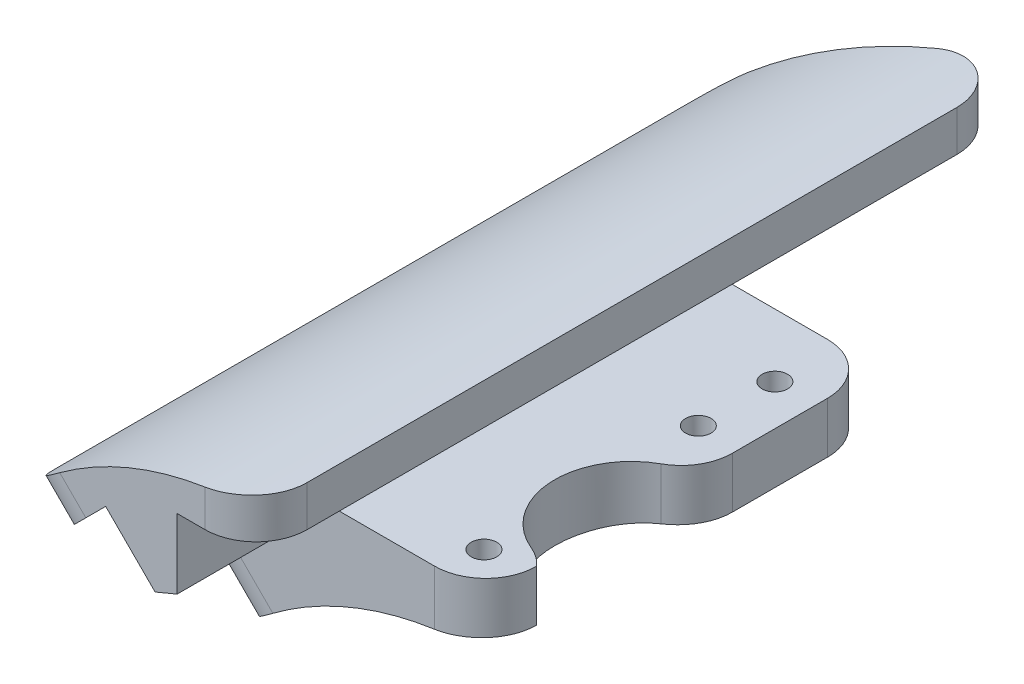
SolidWorks part; units mm, degrees
ref_plane "Front Plane" through (0, 0, 0) normal (0, 0, 1) x (1, 0, 0)
ref_plane "Top Plane" through (0, 0, 0) normal (0, 1, 0) x (1, 0, 0)
ref_plane "Right Plane" through (0, 0, 0) normal (1, 0, 0) x (0, 0, -1)
sketch "Sketch1" plane through (0, 0, 0) normal (0, 0, 1) x (1, 0, 0)
  line L0 (301.4111, 21.2) -> (301.4111, -10.5) construction
  line L1 (260.9608, -3.5551) -> (271.9209, 7.4051)
  line L2 (255.3039, 2.1018) -> (277.7192, -20.3135) construction
  line L3 (277.7192, -20.3135) -> (287.5327, -10.5) construction
  line L4 (276.4111, 2.2079) -> (265.8045, -8.3987) construction
  line L5 (271.9209, 7.4051) -> (281.6083, -2.2823)
  line L6 (286.4111, 6.35) -> (301.4111, 6.35) construction
  line L7 (255.3039, 2.1018) -> (274.4021, 21.2) construction
  line L8 (274.4021, 21.2) -> (301.4111, 21.2) construction
  line L9 (287.5327, -10.5) -> (301.4111, -10.5) construction
  line L10 (271.9209, 6.698) -> (280.9012, -2.2823) construction
  line L11 (286.4111, 0) -> (286.4111, 12.7) construction
  line L12 (281.6083, -2.2823) -> (270.6482, -13.2424)
  line L13 (301.4111, 13.2) -> (285.9111, 13.2)
  line L14 (285.9111, 13.2) -> (285.9111, -0.5)
  line L15 (285.9111, -0.5) -> (301.4111, -0.5)
  line L16 (286.4111, 12.7) -> (286.4111, 13.2) construction
  line L17 (286.4111, 12.7) -> (285.9111, 12.7) construction
  line L18 (271.9209, 6.698) -> (272.2745, 7.0515) construction
  line L19 (271.9209, 6.698) -> (271.5674, 7.0515) construction
  line L20 (271.9209, 6.698) -> (260.8822, -4.3407) construction
  line L21 (255.3039, 2.1018) -> (260.9608, -3.5551)
  line L22 (270.6482, -13.2424) -> (277.7192, -20.3135) construction
  line L23 (301.4111, 21.2) -> (301.4111, 13.2)
  line L24 (301.4111, -0.5) -> (301.4111, -10.5) construction
  line L25 (270.6482, -13.2424) -> (260.0416, -23.849)
  line L26 (260.0416, -23.849) -> (267.1126, -30.9201)
  line L27 (267.1126, -30.9201) -> (277.7192, -20.3135) construction
  line L28 (301.4111, -0.5) -> (316.4111, -0.5)
  line L29 (316.4111, -0.5) -> (316.4111, -10.5)
  line L30 (316.4111, -10.5) -> (301.4111, -10.5) construction
  arc A0 (255.3039, 2.1018) -> (301.4111, 21.2) centre (301.4111, -44.0053) cw
  arc A1 (277.7192, -20.3135) -> (301.4111, -10.5) centre (301.4111, -44.0053) cw construction
  arc A2 (316.4111, -10.5) -> (267.1126, -30.9201) centre (316.4111, -80.2185) ccw
  point P9 (276.4111, 2.2079)
  point P21 (286.4111, 6.35)
  point P27 (285.9111, 6.35)
  point P39 (276.7646, 2.5614)
  dimension "D3" = 0.5
  dimension "D1" = 15
  dimension "D2" = 10
  dimension "D4" = 8
  dimension "D5" = 15
extrude "Boss-Extrude1" add sketch "Sketch1" against normal blind 170
sketch "Sketch2" plane through (0, 0, 0) normal (0, 1, 0) x (1, 0, 0)
  line L0 (255.3039, 135) -> (255.3039, 170)
  line L1 (255.3039, 170) -> (316.4111, 170)
  line L2 (316.4111, 170) -> (316.4111, 157)
  line L4 (255.3039, 170) -> (255.3039, 0) construction
  line L10 (316.4111, 157) -> (255.3039, 135)
  line L13 (271.9209, 6.5651) -> (271.9209, 140.7896)
  line L14 (215.8519, 111.3845) -> (152.8822, 110.4773)
  line L15 (109.2864, 27.2949) -> (213.7889, 28.8005)
  line L16 (271.9209, 6.5651) -> (271.9209, 140.7896) construction
  line L17 (215.8519, 111.3845) -> (152.8822, 110.4773) construction
  line L18 (109.2864, 27.2949) -> (213.7889, 28.8005) construction
  line L19 (301.4111, 148.0263) -> (316.4111, 157) construction
  line L20 (301.4111, 170) -> (301.4111, 0) construction
  line L24 (306.9477, 3) -> (1335.5726, 3)
  line L25 (1335.5726, 3) -> (1335.5726, 146.6245)
  line L27 (1335.5726, 146.6245) -> (1335.5727, 146.6245)
  line L28 (1335.5727, 146.6245) -> (1335.4979, 146.6677)
  line L29 (286.5038, 140.8468) -> (286.4109, 140.7896)
  line L30 (286.4109, 140.7896) -> (286.4111, 140.7896)
  line L31 (286.4111, 140.7896) -> (286.4111, 5.6809)
  line L32 (306.9477, 3) -> (1335.5726, 3) construction
  line L33 (1335.5726, 3) -> (1335.5726, 146.6245) construction
  line L34 (1335.5726, 146.6245) -> (1335.5727, 146.6245) construction
  line L35 (1335.5727, 146.6245) -> (1335.4979, 146.6677) construction
  line L36 (286.5038, 140.8468) -> (286.4109, 140.7896) construction
  line L37 (286.4109, 140.7896) -> (286.4111, 140.7896) construction
  line L38 (286.4111, 140.7896) -> (286.4111, 5.6809) construction
  arc A8 (1335.4979, 146.6677) -> (1320.4172, 153.4031) centre (1295.5076, 77.38) ccw
  arc A9 (1320.4172, 153.4031) -> (302.7902, 148.4937) centre (818.975, -1376.9807) ccw
  arc A10 (302.7902, 148.4937) -> (286.5038, 140.8468) centre (328.4321, 72.7144) ccw
  arc A11 (286.4111, 5.6809) -> (306.9477, 3) centre (306.9477, 83) ccw
  arc A12 (1335.4979, 146.6677) -> (1320.4172, 153.4031) centre (1295.5076, 77.38) ccw construction
  arc A13 (1320.4172, 153.4031) -> (302.7902, 148.4937) centre (818.975, -1376.9807) ccw construction
  arc A14 (302.7902, 148.4937) -> (286.5038, 140.8468) centre (328.4321, 72.7144) ccw construction
  arc A15 (286.4111, 5.6809) -> (306.9477, 3) centre (306.9477, 83) ccw construction
  ellipse E12 centre (287.1497, 83.6117) end of major axis (287.1497, 163.6117) minor radius 56.5685 (260.8822, 12.7594) -> (271.9209, 6.5651) ccw
  ellipse E13 centre (174.6096, 366.8617) end of major axis (174.6096, 102.1967) minor radius 187.1464 (232.8929, 115.3588) -> (271.9209, 140.7896) ccw
  ellipse E14 centre (215.2757, 191.3803) end of major axis (215.2757, 111.3803) minor radius 56.5685 (215.8519, 111.3845) -> (232.8929, 115.3588) ccw
  ellipse E15 centre (153.2424, 60.4799) end of major axis (153.2424, 110.4799) minor radius 35.3553 (152.8822, 110.4773) -> (128.7312, 96.5133) ccw
  ellipse E16 centre (172.8513, 31.6532) end of major axis (172.8513, 121.6532) minor radius 63.6396 (128.7312, 96.5133) -> (109.2864, 27.2949) ccw
  ellipse E17 centre (214.7999, -111.5406) end of major axis (214.7999, -251.889) minor radius 99.2413 (260.8822, 12.7594) -> (213.7889, 28.8005) ccw
  ellipse E18 centre (287.1497, 83.6117) end of major axis (287.1497, 163.6117) minor radius 56.5685 (260.8822, 12.7594) -> (271.9209, 6.5651) ccw construction
  ellipse E19 centre (174.6096, 366.8617) end of major axis (174.6096, 102.1967) minor radius 187.1464 (232.8929, 115.3588) -> (271.9209, 140.7896) ccw construction
  ellipse E20 centre (215.2757, 191.3803) end of major axis (215.2757, 111.3803) minor radius 56.5685 (215.8519, 111.3845) -> (232.8929, 115.3588) ccw construction
  ellipse E21 centre (153.2424, 60.4799) end of major axis (153.2424, 110.4799) minor radius 35.3553 (152.8822, 110.4773) -> (128.7312, 96.5133) ccw construction
  ellipse E22 centre (172.8513, 31.6532) end of major axis (172.8513, 121.6532) minor radius 63.6396 (128.7312, 96.5133) -> (109.2864, 27.2949) ccw construction
  ellipse E23 centre (214.7999, -111.5406) end of major axis (214.7999, -251.889) minor radius 99.2413 (260.8822, 12.7594) -> (213.7889, 28.8005) ccw construction
  point P4 (306.4111, 170)
  point P31 (321.4111, 160.1178)
  point P33 (251.7683, 134.9943)
  point P38 (321.4111, 163.6117)
  point P39 (0, 0)
  dimension "D1" = 0
  dimension "D3" = 35
  dimension "D4" = 13
  dimension "D2" = 0
extrude "Cut-Extrude1" cut sketch "Sketch2" against normal through all both and the other way through all
ref_plane "Plane3" through (50.0496, -120.8305, 0) normal (0.3827, -0.9239, 0) x (-0.9239, -0.3827, 0)
sketch "Sketch11" plane through (50.0496, -120.8305, 0) normal (0.3827, -0.9239, 0) x (-0.9239, -0.3827, 0)
  line L0 (-231.1204, 136.7057) -> (-231.1204, 0) construction
  line L1 (-292.1344, 157) -> (-231.1204, 157)
  line L2 (-292.1344, 157) -> (-292.1344, 107)
  line L3 (-292.1344, 107) -> (-231.1204, 107)
  line L4 (-231.1204, 157) -> (-231.1204, 107)
  line L5 (-292.1344, 157) -> (-231.1204, 107) construction
  line L6 (-292.1344, 107) -> (-231.1204, 157) construction
  line L8 (-292.1344, 0) -> (-231.1204, 0)
  line L9 (-292.1344, 0) -> (-292.1344, 30)
  line L10 (-292.1344, 30) -> (-231.1204, 30)
  line L11 (-231.1204, 0) -> (-231.1204, 30)
  line L12 (-292.1344, 0) -> (-231.1204, 30) construction
  line L13 (-292.1344, 30) -> (-231.1204, 0) construction
  point P4 (-261.6274, 132)
  point P12 (-261.6274, 15)
  dimension "D1" = 30
  dimension "D2" = 50
extrude "Cut-Extrude10" cut sketch "Sketch11" against normal up to vertex (20.9106 mm away) up to point (281.6083, -2.2823, 0)
fillet "Fillet1" radius 10 8 edges at (258.1324, -0.7266, -136.0183) (258.1324, -0.7266, 0) (301.4111, 17.2, 0) (301.4111, 17.2, -151.5996) (316.4111, -5.5, -30) (263.5771, -27.3846, -30) (263.5771, -27.3846, -107) (316.4111, -5.5, -107)
ref_plane "Plane1" through (0, -10.5, 0) normal (0, 1, 0) x (0, 0, 1)
ref_plane "Plane2" through (149.0164, -149.0164, 0) normal (0.7071, -0.7071, 0) x (0, 0, 1)
sketch "Sketch3" plane through (0, -10.5, 0) normal (0, 1, 0) x (0, 0, -1)
  circle A0 centre (56.4388, -318.485) radius 15
  circle A1 centre (56.4388, -318.485) radius 8.45 construction
  dimension "D1" = 30
extrude "Cut-Extrude6" cut sketch "Sketch3" against normal through all both and the other way through all
sketch "Sketch6" plane through (149.0164, -149.0164, 0) normal (0.7071, -0.7071, 0) x (0, 0, 1)
  line L1 (-38.5, -175.0133) -> (-98.5, -175.0133) construction
  line L2 (-97, -167.0133) -> (-40, -167.0133) construction
  circle A0 centre (-38.5, -175.0133) radius 2.5
  circle A1 centre (-68.5, -175.0133) radius 2.5
  circle A2 centre (-98.5, -175.0133) radius 2.5
  point P0 (-68.5, -175.0133)
  point P3 (-37.6031, -175.0133)
  point P7 (-68.5, -175.0133)
  point P11 (0, 0)
  point P12 (0, 0)
  point P13 (-68.5, -167.0133)
  dimension "D2" = 5
  dimension "D1" = 8
  dimension "D3" = 30
extrude "Cut-Extrude5" cut sketch "Sketch6" against normal through all both and the other way through all
sketch "Sketch7" plane through (149.0164, -149.0164, 0) normal (0.7071, -0.7071, 0) x (0, 0, 1)
  circle A0 centre (-38.5, -175.0133) radius 5
  circle A1 centre (-68.5, -175.0133) radius 5
  circle A2 centre (-98.5, -175.0133) radius 5
  circle A6 centre (-38.5, -175.0133) radius 2.5 construction
  circle A7 centre (-68.5, -175.0133) radius 2.5 construction
  circle A8 centre (-98.5, -175.0133) radius 2.5 construction
  dimension "D1" = 10
extrude "Cut-Extrude7" cut sketch "Sketch7" along normal up to next
sketch "Sketch8" plane through (0, -10.5, 0) normal (0, 1, 0) x (0, 0, 1)
  line L1 (-107, 316.4111) -> (-30, 316.4111) construction
  line L3 (-97, 316.4111) -> (-71.2947, 316.4111) construction
  line L4 (-107, 306.4111) -> (-107, 274.6934) construction
  line L5 (-30, 274.6934) -> (-30, 306.4111) construction
  line L6 (-67.5526, 308.4111) -> (-106.798, 308.4111) construction
  line L7 (-94.6753, 308.4111) -> (-79.6753, 308.4111) construction
  line L8 (-30, 308.4111) -> (-45.325, 308.4111) construction
  circle A0 centre (-79.6753, 308.4111) radius 2.5
  circle A1 centre (-94.6753, 308.4111) radius 2.5
  circle A2 centre (-37.6625, 308.4111) radius 2.5
  arc A3 (-71.2947, 316.4111) -> (-41.5829, 316.4111) centre (-56.4388, 318.485) ccw construction
  arc A4 (-71.2947, 316.4111) -> (-41.5829, 316.4111) centre (-56.4388, 318.485) ccw construction
  arc A5 (-97, 316.4111) -> (-107, 306.4111) centre (-97, 306.4111) ccw construction
  point P6 (-37.6625, 308.4111)
  point P22 (-68.5, 316.4111)
  point P25 (-68.5, 308.4111)
  point P32 (-34.1552, 308.4111)
  point P33 (0, 0)
  point P36 (-87.1753, 308.4111)
  dimension "D2" = 5
  dimension "D1" = 8
  dimension "D3" = 15
extrude "Cut-Extrude8" cut sketch "Sketch8" against normal through all both and the other way through all
sketch "Sketch9" plane through (0, -10.5, 0) normal (0, 1, 0) x (0, 0, 1)
  circle A0 centre (-79.6753, 308.4111) radius 5
  circle A1 centre (-94.6753, 308.4111) radius 5
  circle A2 centre (-37.6625, 308.4111) radius 5
  circle A3 centre (-37.6625, 308.4111) radius 2.5 construction
  circle A4 centre (-79.6753, 308.4111) radius 2.5 construction
  circle A5 centre (-94.6753, 308.4111) radius 2.5 construction
  dimension "D1" = 10
extrude "Cut-Extrude9" cut sketch "Sketch9" against normal up to next
fillet "Fillet2" radius 10 2 edges at (316.4111, -5.5, -71.2947) (316.4111, -5.5, -41.5829)
